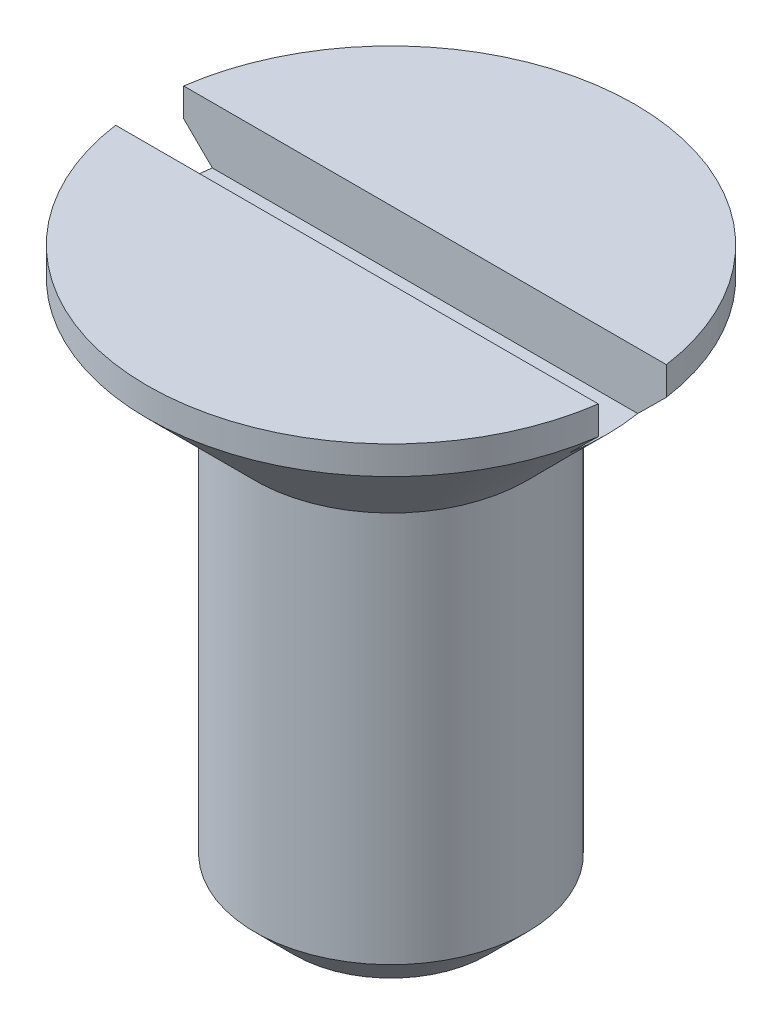
SolidWorks part; units mm, degrees
ref_plane "Спереди" through (0, 0, 0) normal (0, 0, 1) x (1, 0, 0)
ref_plane "Сверху" through (0, 0, 0) normal (0, 1, 0) x (1, 0, 0)
ref_plane "Справа" through (0, 0, 0) normal (1, 0, 0) x (0, 0, -1)
sketch "Эскиз1" plane through (0, 0, 0) normal (0, 0, 1) x (1, 0, 0)
  line L0 (0, 125.7632) -> (0, 0) construction
  line L2 (0, 92.035) -> (0, 67.035)
  line L3 (0, 92.035) -> (10.75, 92.035)
  line L4 (6, 86.035) -> (6, 67.035)
  line L5 (6, 86.035) -> (10.75, 90.785)
  line L6 (6, 67.035) -> (0, 67.035)
  line L7 (10.75, 92.035) -> (10.75, 90.785)
  dimension "D1" = 10.75
  dimension "D2" = 25
  dimension "D3" = 6
  dimension "D5" = 6
revolve "Повернуть1" add sketch "Эскиз1" angle 360 about L0
ref_axis "Ось4" through (0, 10.0338, 0) along (0, -1, 0)
sketch "Эскиз13" plane through (0, 92.035, 0) normal (0, 1, 0) x (-1, 0, 0)
  line L1 (10.75, -1.5) -> (-10.75, -1.5)
  line L2 (10.75, -1.5) -> (10.75, 1.5)
  line L3 (10.75, 1.5) -> (-10.75, 1.5)
  line L4 (-10.75, -1.5) -> (-10.75, 1.5)
  dimension "D1" = 10.75
  dimension "D2" = 21.5
  dimension "D3" = 1.5
  dimension "D4" = 3
extrude "Вырез-Вытянуть9" cut sketch "Эскиз13" against normal blind 2.5
chamfer "Фаска1" distance 1.75 angle 45 1 edges at (-6, 67.035, 0)
